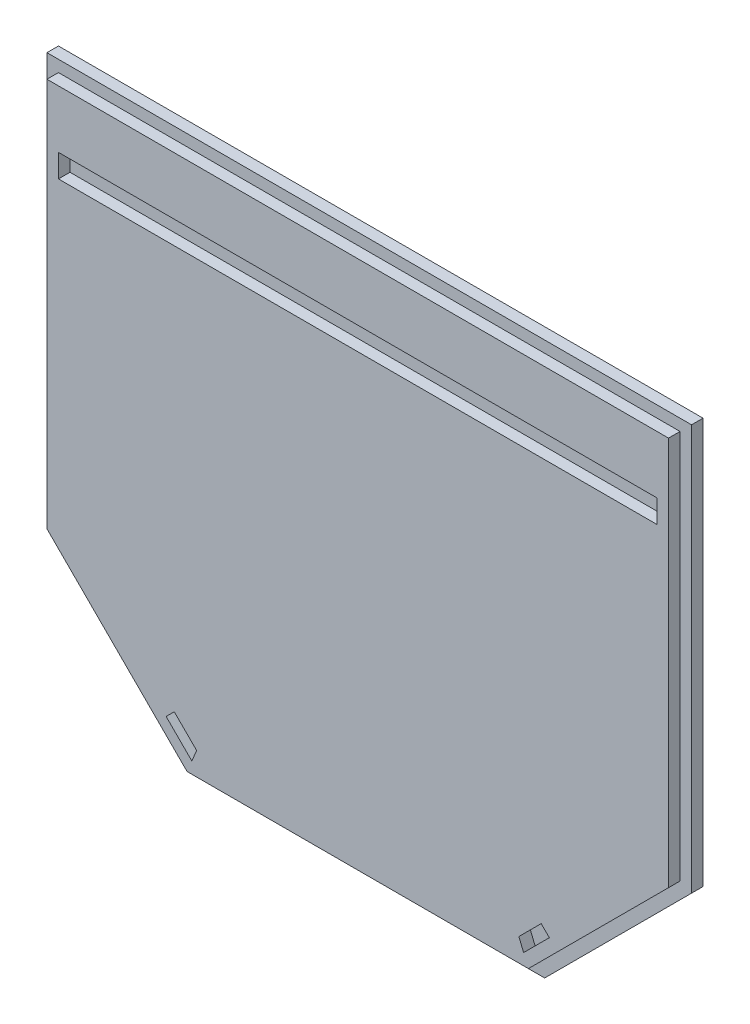
SolidWorks part; units mm, degrees
ref_plane "Front Plane" through (0, 0, 0) normal (0, 0, 1) x (1, 0, 0)
ref_plane "Top Plane" through (0, 0, 0) normal (0, 1, 0) x (1, 0, 0)
ref_plane "Right Plane" through (0, 0, 0) normal (1, 0, 0) x (0, 0, -1)
sketch "Sketch1" plane through (0, 0, 0) normal (0, 0, 1) x (1, 0, 0)
  line L0 (0, 0) -> (355.6, 0)
  line L1 (0, 0) -> (0, -223.774)
  line L2 (81.026, -304.8) -> (274.574, -304.8)
  line L3 (355.6, -223.774) -> (355.6, 0)
  line L4 (81.026, -304.8) -> (63.0655, -286.8395)
  line L5 (63.0655, -286.8395) -> (0, -223.774)
  line L6 (177.8, -304.8) -> (177.8, 0) construction
  line L7 (292.5345, -286.8395) -> (355.6, -223.774)
  line L8 (274.574, -304.8) -> (292.5345, -286.8395)
  dimension "D1" = 355.6
  dimension "D2" = 193.548
  dimension "D4" = 25.4
  dimension "D5" = 45
  dimension "D9" = 304.8
extrude "Boss-Extrude1" add sketch "Sketch1" along normal blind 12.7
sketch "Sketch2" plane through (0, 0, 12.7) normal (0, 0, 1) x (1, 0, 0)
  line L0 (6.35, -221.1437) -> (83.6563, -298.45)
  line L1 (83.6563, -298.45) -> (271.9437, -298.45)
  line L2 (271.9437, -298.45) -> (349.25, -221.1437)
  line L3 (349.25, -221.1437) -> (349.25, -6.35)
  line L4 (349.25, -6.35) -> (6.35, -6.35)
  line L5 (6.35, -6.35) -> (6.35, -221.1437)
  line L6 (0, -223.774) -> (81.026, -304.8) construction
  line L7 (81.026, -304.8) -> (274.574, -304.8) construction
  line L8 (274.574, -304.8) -> (355.6, -223.774) construction
  line L9 (355.6, -223.774) -> (355.6, 0) construction
  line L10 (0, 0) -> (0, -223.774) construction
  line L11 (355.6, 0) -> (0, 0) construction
  line L27 (0, 0) -> (0, -223.774)
  line L28 (0, -223.774) -> (81.026, -304.8)
  line L29 (81.026, -304.8) -> (274.574, -304.8)
  line L30 (274.574, -304.8) -> (355.6, -223.774)
  line L31 (355.6, -223.774) -> (355.6, 0)
  line L32 (355.6, 0) -> (0, 0)
  line L34 (12.7, -38.1) -> (342.9, -38.1)
  line L35 (12.7, -38.1) -> (12.7, -50.8)
  line L36 (12.7, -50.8) -> (342.9, -50.8)
  line L37 (342.9, -38.1) -> (342.9, -50.8)
  line M13 (0, 0) -> (0, -223.774)
  line M14 (0, -223.774) -> (81.026, -304.8)
  line M15 (81.026, -304.8) -> (274.574, -304.8)
  line M16 (274.574, -304.8) -> (355.6, -223.774)
  line M17 (355.6, -223.774) -> (355.6, 0)
  line M18 (355.6, 0) -> (0, 0)
  dimension "D2" = 6.35
  dimension "D3" = 6.35
  dimension "D4" = 6.35
  dimension "D5" = 6.35
  dimension "D6" = 6.35
  dimension "D7" = 6.35
  dimension "D8" = 6.35
  dimension "D9" = 50.8
  dimension "D10" = 12.7
extrude "Cut-Extrude1" cut sketch "Sketch2" against normal blind 6.35 contours L37 L34 L35 L36 | L5 L4 L3 L2 L1 L0 M18 M13 M14 M15 M16 M17 region at (177.8, -4.6835, 12.7) region at (177.8, -44.45, 12.7)
sketch "Sketch3" plane through (0, 0, 12.7) normal (0, 0, 1) x (1, 0, 0)
  line L0 (177.8, -304.8) -> (177.8, 0) construction
  line L1 (81.026, -304.8) -> (274.574, -304.8) construction
  line L2 (355.6, 0) -> (0, 0) construction
  line L3 (81.026, -304.8) -> (83.6563, -298.45) construction
  line L4 (86.2865, -292.1) -> (72.0977, -277.9112)
  line L5 (86.2865, -292.1) -> (88.9168, -285.75)
  line L8 (72.0977, -277.9112) -> (76.5878, -273.4211)
  line L9 (76.5878, -273.4211) -> (88.9168, -285.75)
  line L10 (283.5023, -277.9112) -> (279.0122, -273.4211)
  line L11 (269.3135, -292.1) -> (283.5023, -277.9112)
  line L12 (269.3135, -292.1) -> (266.6832, -285.75)
  line L13 (279.0122, -273.4211) -> (266.6832, -285.75)
  line L14 (11.7799, -215.7138) -> (6.35, -221.1437) construction
  line L15 (6.35, -221.1437) -> (83.6563, -298.45) construction
  point P19 (0, 0)
  dimension "D1" = 20.066
  dimension "D2" = 6.35
  dimension "D3" = 6.35
  dimension "D4" = 90
  dimension "D5" = 67.5
extrude "Cut-Extrude3" cut sketch "Sketch3" against normal blind 6.35
